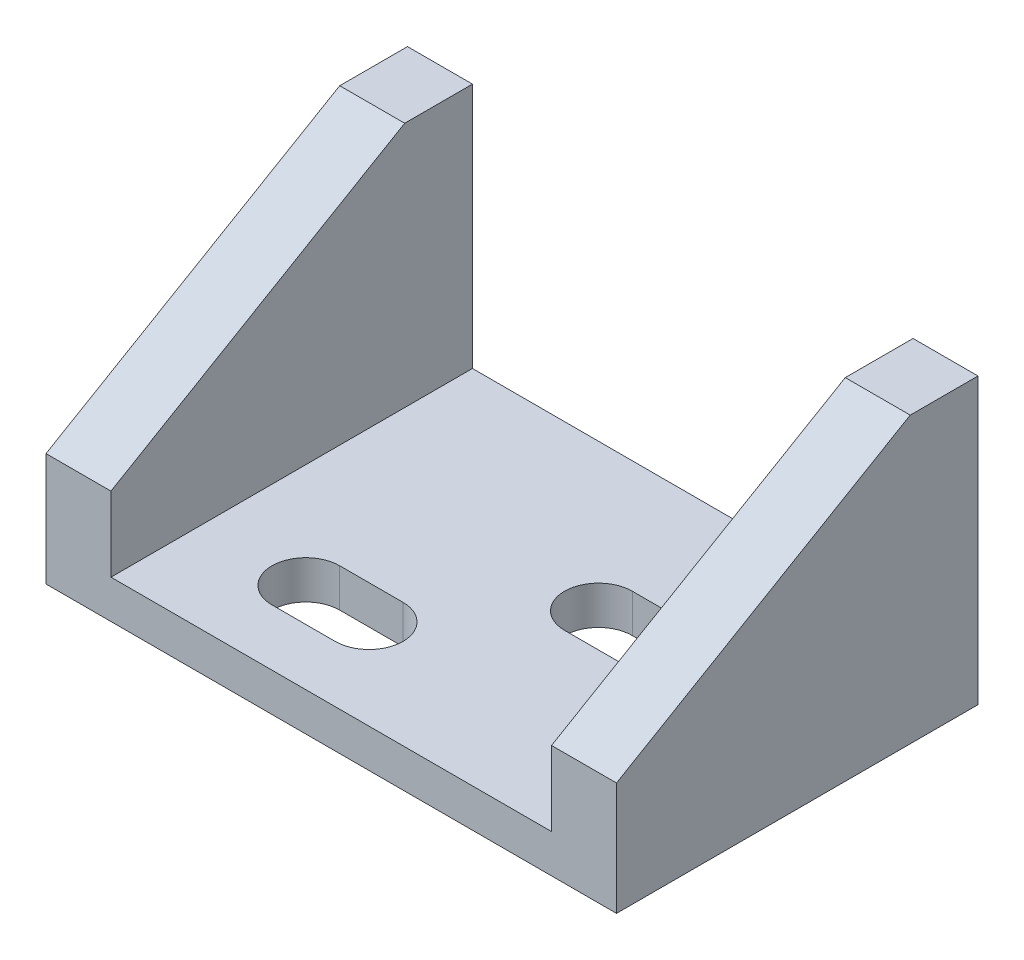
SolidWorks part; units mm, degrees
ref_plane "Front Plane" through (0, 0, 0) normal (0, 0, 1) x (1, 0, 0)
ref_plane "Top Plane" through (0, 0, 0) normal (0, 1, 0) x (1, 0, 0)
ref_plane "Right Plane" through (0, 0, 0) normal (1, 0, 0) x (0, 0, -1)
sketch "Sketch1" plane through (0, 0, 0) normal (0, 1, 0) x (1, 0, 0)
  line L1 (-12.625, 8) -> (12.625, 8)
  line L2 (-12.625, 8) -> (-12.625, -8)
  line L3 (-12.625, -8) -> (12.625, -8)
  line L4 (12.625, 8) -> (12.625, -8)
  line L11 (-55, 0) -> (55, 0) construction
  line L12 (0, -55) -> (0, 55) construction
  dimension "D1" = 25.25
  dimension "D2" = 16
  dimension "D3" = 8
  dimension "D4" = 12.625
extrude "Boss-Extrude1" add sketch "Sketch1" along normal blind 1.7
sketch "Sketch5" plane through (0, 0, 0) normal (1, 0, 0) x (0, 0, -1)
  line L0 (0, 0.935) -> (0, -0.935) construction
  line L1 (-8, 1.7) -> (8, 1.7)
  line L2 (-8, 1.7) -> (-8, 5)
  line L3 (5, 12.6) -> (8, 12.6)
  line L4 (8, 1.7) -> (8, 12.6)
  line L5 (8.8, 0) -> (-8.8, 0) construction
  line L6 (-8, 5) -> (5, 12.6)
  dimension "D1" = 10.9
  dimension "D2" = 16
  dimension "D3" = 8
  dimension "D4" = 1.7
  dimension "D5" = 3.3
  dimension "D6" = 3
extrude "Boss-Extrude3" add sketch "Sketch5" along normal mid plane 25.25
extrude "Cut-Extrude7" cut sketch "Sketch5<2>" against normal mid plane 19.5
sketch "Sketch5<2>" plane through (0, 0, 0) normal (1, 0, 0) x (0, 0, -1) same geometry as "Sketch5"
sketch "Sketch6" plane through (0, 0, 0) normal (0, 1, 0) x (1, 0, 0)
  line L0 (-5.125, -2.5) -> (-2.325, -2.5)
  line L1 (-5.125, -5.5) -> (-2.325, -5.5)
  line L2 (2.325, 0) -> (5.125, 0)
  line L3 (2.325, 3) -> (5.125, 3)
  line L5 (12.625, 5) -> (12.625, -8) construction
  line L6 (-9.75, -8) -> (9.75, -8) construction
  line L7 (-12.625, 5) -> (-12.625, -8) construction
  arc A0 (2.325, 3) -> (2.325, 0) centre (2.325, 1.5) ccw
  arc A1 (5.125, 0) -> (5.125, 3) centre (5.125, 1.5) ccw
  arc A2 (-5.125, -2.5) -> (-5.125, -5.5) centre (-5.125, -4) ccw
  arc A3 (-2.325, -5.5) -> (-2.325, -2.5) centre (-2.325, -4) ccw
  dimension "D1" = 3
  dimension "D2" = 3
  dimension "D3" = 3
  dimension "D4" = 3
  dimension "D5" = 2.8
  dimension "D6" = 2.8
  dimension "D7" = 8
  dimension "D8" = 7.5
  dimension "D9" = 2.5
  dimension "D10" = 7.5
  dimension "D11" = 2.8
extrude "Cut-Extrude8" cut sketch "Sketch6" along normal up to next
